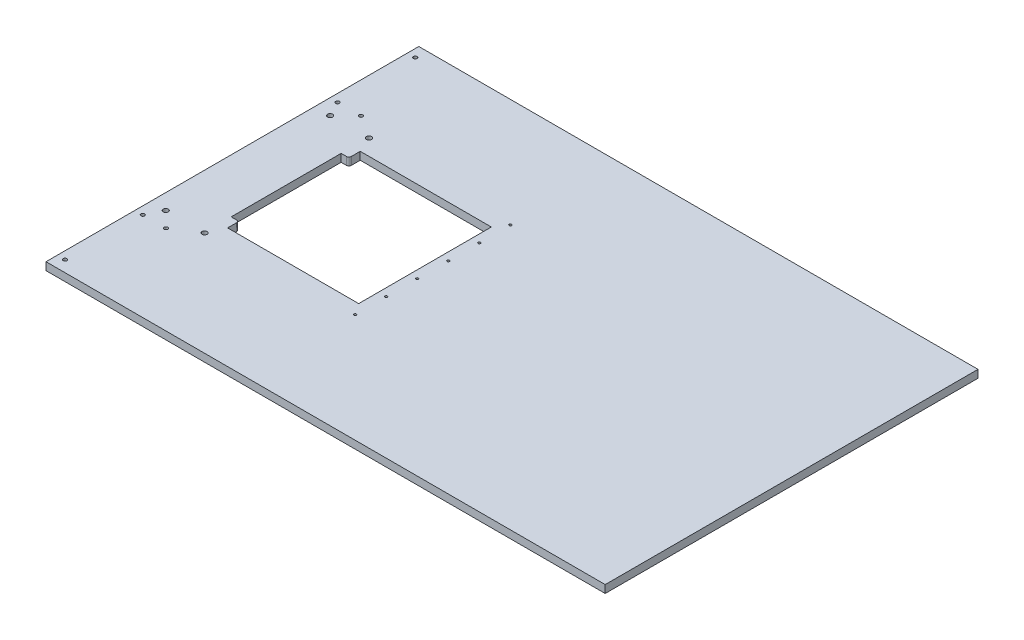
SolidWorks part; units mm, degrees
ref_plane "Front Plane" through (0, 0, 0) normal (0, 0, 1) x (1, 0, 0)
ref_plane "Top Plane" through (0, 0, 0) normal (0, 1, 0) x (1, 0, 0)
ref_plane "Right Plane" through (0, 0, 0) normal (1, 0, 0) x (0, 0, -1)
sketch "Sketch1" plane through (0, 0, 0) normal (0, 1, 0) x (1, 0, 0)
  line L1 (-228.6, -152.4) -> (228.6, -152.4)
  line L2 (-228.6, -152.4) -> (-228.6, 152.4)
  line L3 (-228.6, 152.4) -> (228.6, 152.4)
  line L4 (228.6, -152.4) -> (228.6, 152.4)
  line L5 (-228.6, -152.4) -> (228.6, 152.4) construction
  line L6 (-228.6, 152.4) -> (228.6, -152.4) construction
  point P0 (0, 0)
  dimension "D1" = 304.8
  dimension "D2" = 457.2
extrude "Boss-Extrude1" add sketch "Sketch1" along normal blind 6.35 contours L3 L4 L1 L2
sketch "Sketch2" plane through (0, 6.35, 0) normal (0, 1, 0) x (1, 0, 0)
  circle A0 centre (-184.15, -67.1976) radius 2.0635 construction
  circle A1 centre (-215.9, -67.1976) radius 2.0635 construction
  circle A2 centre (-184.15, 67.1976) radius 2.0635 construction
  circle A3 centre (-215.9, 67.1976) radius 2.0635 construction
  circle A6 centre (-184.15, -67.1976) radius 2.0635
  circle A7 centre (-215.9, -67.1976) radius 2.0635
  circle A8 centre (-184.15, 67.1976) radius 2.0635
  circle A9 centre (-215.9, 67.1976) radius 2.0635
extrude "Cut-Extrude1" cut sketch "Sketch2" against normal through all
sketch "Sketch3" plane through (0, 6.35, 0) normal (0, 1, 0) x (1, 0, 0)
  line L0 (-228.6, 0) -> (228.6, 0) construction
  line L1 (-228.6, -152.4) -> (-228.6, 152.4) construction
  line L2 (228.6, -152.4) -> (228.6, 152.4) construction
sketch "Sketch4" plane through (0, 6.35, 0) normal (0, 1, 0) x (1, 0, 0)
  line L0 (-184.658, 44.958) -> (-184.658, -44.958)
  line L1 (-184.658, -44.958) -> (-180.34, -44.958)
  line L2 (-178.308, -46.99) -> (-178.308, -54.229)
  line L3 (-178.308, -54.229) -> (-71.12, -54.229)
  line L4 (-71.12, -54.229) -> (-71.12, 54.229)
  line L5 (-71.12, 54.229) -> (-178.308, 54.229)
  line L6 (-178.308, 54.229) -> (-178.308, 46.99)
  line L7 (-180.34, 44.958) -> (-184.658, 44.958)
  line L8 (-184.15, 44.45) -> (-184.15, -44.45)
  line L9 (-180.34, 44.45) -> (-184.15, 44.45)
  line L10 (-177.8, 53.721) -> (-177.8, 46.99)
  line L11 (-71.628, 53.721) -> (-177.8, 53.721)
  line L12 (-71.628, -53.721) -> (-71.628, 53.721)
  line L13 (-177.8, -53.721) -> (-71.628, -53.721)
  line L14 (-177.8, -46.99) -> (-177.8, -53.721)
  line L15 (-184.15, -44.45) -> (-180.34, -44.45)
  line L16 (-184.15, 44.45) -> (-184.15, -44.45) construction
  line L17 (-180.34, 44.45) -> (-184.15, 44.45) construction
  line L18 (-177.8, 53.721) -> (-177.8, 46.99) construction
  line L19 (-71.628, 53.721) -> (-177.8, 53.721) construction
  line L20 (-71.628, -53.721) -> (-71.628, 53.721) construction
  line L21 (-177.8, -53.721) -> (-71.628, -53.721) construction
  line L22 (-177.8, -46.99) -> (-177.8, -53.721) construction
  line L23 (-184.15, -44.45) -> (-180.34, -44.45) construction
  arc A0 (-178.308, -46.99) -> (-180.34, -44.958) centre (-180.34, -46.99) ccw
  arc A1 (-180.34, 44.958) -> (-178.308, 46.99) centre (-180.34, 46.99) ccw
  arc A2 (-180.34, 44.45) -> (-177.8, 46.99) centre (-180.34, 46.99) ccw
  arc A3 (-177.8, -46.99) -> (-180.34, -44.45) centre (-180.34, -46.99) ccw
  arc A4 (-180.34, 44.45) -> (-177.8, 46.99) centre (-180.34, 46.99) ccw construction
  arc A5 (-177.8, -46.99) -> (-180.34, -44.45) centre (-180.34, -46.99) ccw construction
  dimension "D1" = 0
  dimension "D2" = 0.508
extrude "Cut-Extrude2" cut sketch "Sketch4" against normal up to next
sketch "Sketch5" plane through (0, 6.35, 0) normal (0, 1, 0) x (1, 0, 0)
  circle A0 centre (-203.2, 79.629) radius 1.5 construction
  circle A1 centre (-222.25, 143.129) radius 1.5 construction
  circle A2 centre (-222.25, 79.629) radius 1.5 construction
  circle A3 centre (-203.2, -79.629) radius 1.5 construction
  circle A4 centre (-222.25, -79.629) radius 1.5 construction
  circle A5 centre (-222.25, -143.129) radius 1.5 construction
  circle A6 centre (-203.2, 79.629) radius 1.5
  circle A7 centre (-222.25, 143.129) radius 1.5
  circle A8 centre (-222.25, 79.629) radius 1.5
  circle A9 centre (-203.2, -79.629) radius 1.5
  circle A10 centre (-222.25, -79.629) radius 1.5
  circle A11 centre (-222.25, -143.129) radius 1.5
extrude "Cut-Extrude3" cut sketch "Sketch5" against normal through all
sketch "Sketch6" plane through (0, 6.35, 0) normal (0, 1, 0) x (1, 0, 0)
  circle A11 centre (-64.77, -12.7) radius 1
  circle A12 centre (-64.77, -12.7) radius 1
  circle A13 centre (-64.77, 12.7) radius 1
  circle A14 centre (-64.77, 12.7) radius 1
  circle A15 centre (-64.77, 38.1) radius 1
  circle A16 centre (-64.77, 38.1) radius 1
  circle A17 centre (-64.77, 63.5) radius 1
  circle A18 centre (-64.77, 63.5) radius 1
  circle A19 centre (-64.77, -63.5) radius 1
  circle A20 centre (-64.77, -63.5) radius 1
  circle A21 centre (-64.77, -38.1) radius 1
  circle A22 centre (-64.77, -38.1) radius 1
  dimension "D1" = 0
  dimension "D2" = 0
  dimension "D3" = 0
  dimension "D4" = 0
  dimension "D5" = 0
  dimension "D6" = 0
extrude "Cut-Extrude4" cut sketch "Sketch6" against normal through all
equation "\"tightTol\" = 0.005in"
equation "\"normTol\"= 0.01in"
equation "\"looseTol\"= 0.02in"
equation "\"D2@Sketch4\"=\"looseTol\""
